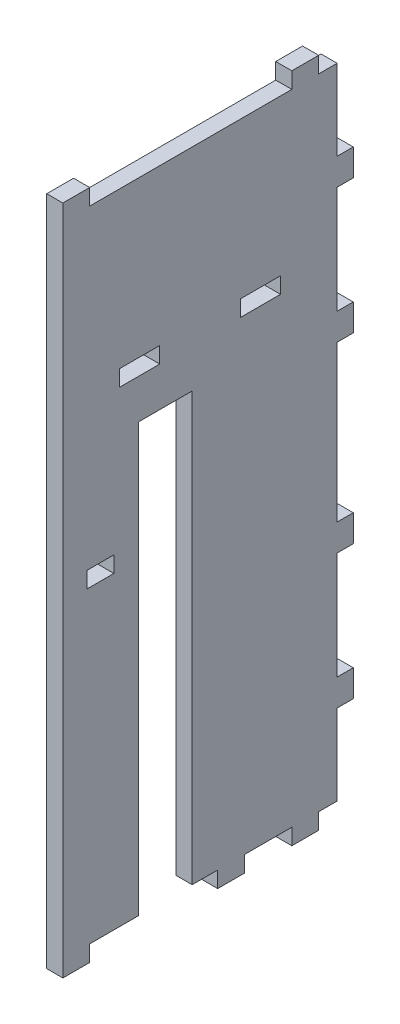
SolidWorks part; units mm, degrees
ref_plane "Plan de face" through (0, 0, 0) normal (0, 0, 1) x (1, 0, 0)
ref_plane "Plan de dessus" through (0, 0, 0) normal (0, 1, 0) x (1, 0, 0)
ref_plane "Plan de droite" through (0, 0, 0) normal (1, 0, 0) x (0, 0, -1)
sketch "Esquisse1" plane through (0, 0, 0) normal (1, 0, 0) x (0, 0, -1)
  line L0 (97.1531, 0) -> (-102.2664, 0) construction
  line L1 (-51.085, 119) -> (51.085, 119)
  line L2 (-51.085, 119) -> (-51.085, -119)
  line L3 (-51.085, -119) -> (51.085, -119)
  line L4 (51.085, 119) -> (51.085, -119)
  line L5 (0, 172.7153) -> (0, -236.1933) construction
  line L7 (-42.085, 2) -> (-32.085, 2)
  line L8 (-42.085, 2) -> (-42.085, -4)
  line L9 (-42.085, -4) -> (-32.085, -4)
  line L10 (-32.085, 2) -> (-32.085, -4)
  line L15 (-30, 61) -> (-15, 61)
  line L16 (-30, 61) -> (-30, 55)
  line L17 (-30, 55) -> (-15, 55)
  line L18 (-15, 61) -> (-15, 55)
  line L19 (15, 61) -> (30, 61)
  line L20 (15, 61) -> (15, 55)
  line L21 (15, 55) -> (30, 55)
  line L22 (30, 61) -> (30, 55)
  dimension "D1" = 238
  dimension "D2" = 102.17
  dimension "D4" = 119
  dimension "D13" = 15
  dimension "D14" = 15
  dimension "D15" = 30
  dimension "D16" = 6
  dimension "D17" = 6
  dimension "D3" = 51.085
  dimension "D5" = 58
  dimension "D6" = 21.085
  dimension "D7" = 9
  dimension "D8" = 117
  dimension "D9" = 6
  dimension "D10" = 10
extrude "Boss.-Extru.1" add sketch "Esquisse1" along normal blind 6
sketch "Esquisse3" plane through (6, 0, 0) normal (1, 0, 0) x (0, 0, -1)
  line L0 (-51.085, -119) -> (51.085, -119) construction
  line L1 (-51.085, -119) -> (-41.085, -119)
  line L2 (-51.085, -119) -> (-51.085, -125)
  line L3 (-51.085, -125) -> (-41.085, -125)
  line L4 (-41.085, -119) -> (-41.085, -125)
  line L5 (245.3741, 0) -> (-166.5298, 0) construction
  line L6 (51.085, -119) -> (51.085, 119) construction
  line L7 (34.205, -119) -> (44.205, -119)
  line L8 (34.205, -119) -> (34.205, -125)
  line L9 (34.205, -125) -> (44.205, -125)
  line L10 (0, 208.6671) -> (0, -232.3841) construction
  line L11 (-51.085, -119) -> (51.085, -119) construction
  line L12 (44.205, -119) -> (44.205, -125)
  line L13 (57.085, 39) -> (57.085, 29)
  line L14 (51.085, 29) -> (57.085, 29)
  line L15 (51.085, 39) -> (51.085, 29)
  line L16 (51.085, 39) -> (57.085, 39)
  line L17 (57.085, 89) -> (57.085, 79)
  line L18 (51.085, 79) -> (57.085, 79)
  line L19 (51.085, 89) -> (51.085, 79)
  line L20 (51.085, 89) -> (57.085, 89)
  line L22 (51.085, -89) -> (57.085, -89)
  line L23 (51.085, -89) -> (51.085, -79)
  line L24 (51.085, -79) -> (57.085, -79)
  line L25 (57.085, -89) -> (57.085, -79)
  line L26 (51.085, -39) -> (57.085, -39)
  line L27 (51.085, -39) -> (51.085, -29)
  line L28 (51.085, -29) -> (57.085, -29)
  line L29 (0, -208.6671) -> (0, 232.3841) construction
  line L30 (6.585, -119) -> (16.585, -119)
  line L31 (6.585, -119) -> (6.585, -125)
  line L32 (6.585, -125) -> (16.585, -125)
  line L33 (16.585, -119) -> (16.585, -125)
  line L35 (57.085, -39) -> (57.085, -29)
  line L46 (44.205, 119) -> (44.205, 125)
  line L47 (34.205, 125) -> (44.205, 125)
  line L48 (34.205, 119) -> (34.205, 125)
  line L49 (34.205, 119) -> (44.205, 119)
  line L50 (-41.085, 119) -> (-41.085, 125)
  line L51 (-51.085, 125) -> (-41.085, 125)
  line L52 (-51.085, 119) -> (-51.085, 125)
  line L53 (-51.085, 119) -> (-41.085, 119)
  dimension "D2" = 10
  dimension "D3" = 6
  dimension "D4" = 10
  dimension "D5" = 6.88
  dimension "D6" = 6
  dimension "D7" = 6
  dimension "D8" = 10
  dimension "D9" = 6
  dimension "D10" = 10
  dimension "D11" = 6
  dimension "D12" = 10
  dimension "D13" = 17.62
  dimension "D14" = 30
  dimension "D15" = 40
extrude "Boss.-Extru.5" add sketch "Esquisse3" against normal blind 6
sketch "Esquisse6" plane through (6, 0, 0) normal (1, 0, 0) x (0, 0, -1)
  line L0 (-41.085, -119) -> (6.585, -119) construction
  line L1 (-22.915, -119) -> (-2.915, -119)
  line L2 (-22.915, -119) -> (-22.915, 40.29)
  line L3 (-22.915, 40.29) -> (-2.915, 40.29)
  line L4 (-2.915, -119) -> (-2.915, 40.29)
  line L5 (51.085, -79) -> (51.085, -39) construction
  line L6 (-41.085, 125) -> (-51.085, 125) construction
  dimension "D1" = 20
  dimension "D2" = 84.71
  dimension "D3" = 54
extrude "Enlèv. mat.-Extru.2" cut sketch "Esquisse6" against normal blind 6
equation "\"D3@Esquisse1\"=\"D2@Esquisse1\"/2"
equation "\"D4@Esquisse1\"=\"D1@Esquisse1\"/2"
